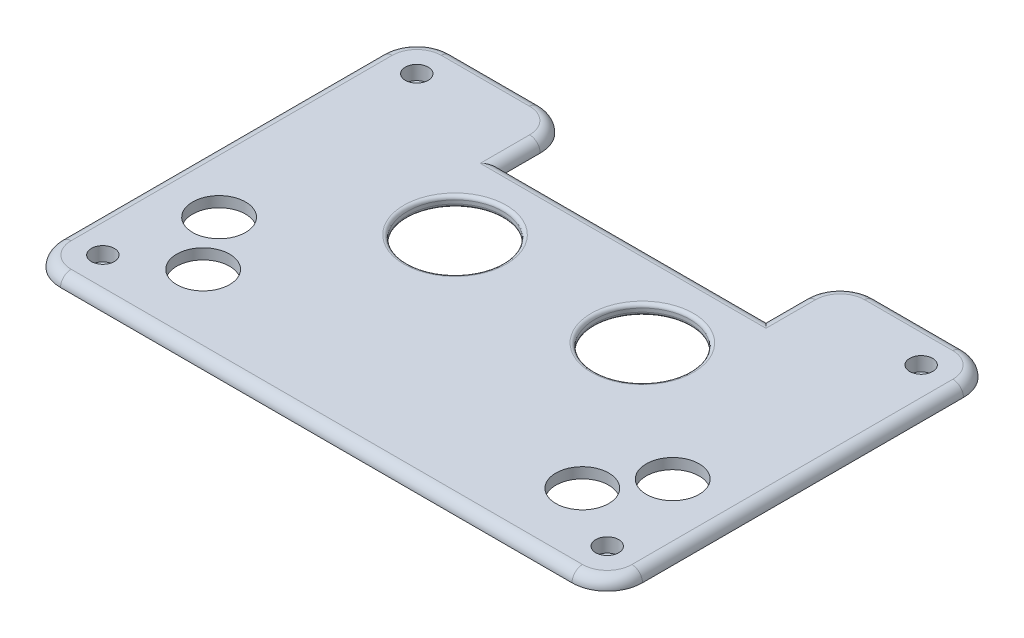
SolidWorks part; units mm, degrees
ref_plane "Front Plane" through (0, 0, 0) normal (0, 0, 1) x (1, 0, 0)
ref_plane "Top Plane" through (0, 0, 0) normal (0, 1, 0) x (1, 0, 0)
ref_plane "Right Plane" through (0, 0, 0) normal (1, 0, 0) x (0, 0, -1)
sketch "Sketch1" plane through (0, 0, 0) normal (0, 1, 0) x (1, 0, 0)
  line L0 (37.5, 55.5) -> (37.5, 34.5)
  line L1 (-82.5, 55.5) -> (82.5, 55.5) construction
  line L2 (-82.5, 55.5) -> (-82.5, -55.5) construction
  line L3 (-82.5, -55.5) -> (82.5, -55.5) construction
  line L4 (82.5, 55.5) -> (82.5, -55.5) construction
  line L5 (-82.5, 55.5) -> (82.5, -55.5) construction
  line L6 (-82.5, -55.5) -> (82.5, 55.5) construction
  line L7 (-82.5, 55.5) -> (-37.5, 55.5) construction
  line L8 (-82.5, 55.5) -> (-82.5, 24.5) construction
  line L10 (-37.5, 55.5) -> (-37.5, 34.5) construction
  line L11 (82.5, 55.5) -> (37.5, 55.5) construction
  line L12 (82.5, 55.5) -> (82.5, 24.5) construction
  line L14 (37.5, 55.5) -> (37.5, 34.5) construction
  line L15 (37.5, 34.5) -> (-37.5, 34.5)
  line L16 (-37.5, 34.5) -> (-37.5, 55.5)
  line L17 (-37.5, 55.5) -> (-82.5, 55.5)
  line L18 (-82.5, 55.5) -> (-82.5, -55.5)
  line L19 (-82.5, -55.5) -> (82.5, -55.5)
  line L20 (82.5, -55.5) -> (82.5, 55.5)
  line L21 (82.5, 55.5) -> (37.5, 55.5)
  point P0 (0, 0)
  dimension "D1" = 45
  dimension "D2" = 21
  dimension "D3" = 75
  dimension "D4" = 165
  dimension "D5" = 45
  dimension "D6" = 111
extrude "Boss-Extrude1" add sketch "Sketch1" along normal blind 3 contours L2 L1 L4 L3 | L21 L0 L15 L16 L17 L18 L19 L20
fillet "Fillet1" radius 10 2 edges at (-82.5, 1.5, 55.5) (82.5, 1.5, 55.5)
fillet "Fillet4" radius 10 4 edges at (-82.5, 1.5, -55.5) (-37.5, 1.5, -55.5) (37.5, 1.5, -55.5) (82.5, 1.5, -55.5)
sketch "Sketch3" plane through (0, 3, 0) normal (0, 1, 0) x (1, 0, 0)
  line L0 (26.55, -6.5946) -> (26.55, 27.4054) construction
  line L7 (39.55, -6.5946) -> (13.55, -6.5946) construction
  line L8 (39.55, -6.5946) -> (39.55, 27.4054) construction
  line L9 (39.55, 27.4054) -> (13.55, 27.4054) construction
  line L10 (13.55, -6.5946) -> (13.55, 27.4054) construction
  line L12 (0, -52.5) -> (0, 31.5) construction
  circle A0 centre (36.6, 24.4554) radius 2.35 construction
  circle A1 centre (36.6, 24.4554) radius 5 construction
  circle A4 centre (36.6, -1.8446) radius 2.35 construction
  circle A5 centre (36.6, -1.8446) radius 5 construction
  circle A6 centre (16.4002, -1.756) radius 5 construction
  circle A7 centre (16.4002, -1.756) radius 2.35 construction
  circle A16 centre (16.5, 24.4554) radius 5 construction
  circle A17 centre (16.5, 24.4554) radius 2.35 construction
  circle A34 centre (26.55, 10.4054) radius 13.5
  circle A35 centre (-26.55, 10.4054) radius 13.5
  dimension "D11" = 4.7
  dimension "D12" = 10
  dimension "D15" = 4.7
  dimension "D16" = 10
  dimension "D2" = 34
  dimension "D3" = 26
  dimension "D9" = 20.2
  dimension "D10" = 27
  dimension "D4" = 4.75
  dimension "D5" = 2.95
  dimension "D6" = 2.95
  dimension "D7" = 2.95
sketch "Sketch5" plane through (0, 3, 0) normal (0, 1, 0) x (1, 0, 0)
  line L0 (-47.5547, -42.6607) -> (-70.4978, -9.8946) construction
  line L1 (-55.7463, -48.3965) -> (-78.6893, -15.6304) construction
  line L2 (-55.7463, -48.3965) -> (-39.3632, -36.925) construction
  line L3 (-39.3632, -36.925) -> (-62.3063, -4.1589) construction
  line L4 (-78.6893, -15.6304) -> (-62.3063, -4.1589) construction
  line L5 (0, -52.5) -> (0, 31.5) construction
  line L8 (-67.2178, -32.0134) -> (-50.8347, -20.5419) construction
  circle A0 centre (-49.2755, -40.2033) radius 1.6 construction
  circle A1 centre (-68.7771, -12.3521) radius 1.6 construction
  circle A2 centre (-49.2755, -40.2033) radius 4 construction
  circle A3 centre (-68.7771, -12.3521) radius 4 construction
  circle A9 centre (-53.7494, -33.8139) radius 7.5
  circle A10 centre (-64.3032, -18.7415) radius 7.5
  circle A11 centre (64.3032, -18.7415) radius 7.5
  circle A12 centre (53.7494, -33.8139) radius 7.5
  dimension "D3" = 3
  dimension "D4" = 3.2
  dimension "D5" = 3.2
  dimension "D6" = 3
  dimension "D7" = 8
  dimension "D8" = 8
  dimension "D9" = 9.2
  dimension "D10" = 15
  dimension "D1" = 40
  dimension "D2" = 20
sketch "Sketch6" plane through (0, 3, 0) normal (0, 1, 0) x (1, 0, 0)
  line L0 (0, -52.5) -> (0, 31.5) construction
  line L14 (76.5, 39.5) -> (66.5, 39.5)
  line L15 (66.5, 49.5) -> (66.5, 39.5)
  line L16 (72.5, 49.5) -> (66.5, 49.5)
  line L18 (76.5, 45.5) -> (76.5, 39.5)
  line L19 (66.5, 44.5) -> (76.5, 44.5) construction
  line L34 (79.5, 0) -> (-79.5, 0) construction
  line L36 (76.5, -45.5) -> (76.5, -39.5)
  line L37 (72.5, -49.5) -> (66.5, -49.5)
  line L38 (66.5, -49.5) -> (66.5, -39.5)
  line L39 (76.5, -39.5) -> (66.5, -39.5)
  line L40 (-76.5, 39.5) -> (-66.5, 39.5)
  line L41 (-76.5, 45.5) -> (-76.5, 39.5)
  line L42 (-66.5, 49.5) -> (-66.5, 39.5)
  line L43 (-72.5, 49.5) -> (-66.5, 49.5)
  line L44 (-72.5, -49.5) -> (-66.5, -49.5)
  line L45 (-76.5, -45.5) -> (-76.5, -39.5)
  line L46 (-76.5, -39.5) -> (-66.5, -39.5)
  line L47 (-66.5, -49.5) -> (-66.5, -39.5)
  arc A11 (76.5, 45.5) -> (72.5, 49.5) centre (72.5, 45.5) ccw
  arc A22 (76.5, -45.5) -> (72.5, -49.5) centre (72.5, -45.5) cw
  arc A23 (-76.5, 45.5) -> (-72.5, 49.5) centre (-72.5, 45.5) cw
  arc A24 (-76.5, -45.5) -> (-72.5, -49.5) centre (-72.5, -45.5) ccw
  point P33 (71.5, 44.5)
  dimension "D3" = 10
  dimension "D4" = 10
extrude "Boss-Extrude4" add sketch "Sketch6" against normal blind 6.9
fillet "Fillet5" radius 3 14 edges at (-37.5, 3, -40) (-40.4289, 3, -52.5711) (-60, 3, -55.5) (-79.5711, 3, -52.5711) (-82.5, 3, 0) (-79.5711, 3, 52.5711) (0, 3, 55.5) (79.5711, 3, 52.5711) (82.5, 3, 0) (79.5711, 3, -52.5711) (37.5, 3, -40) (40.4289, 3, -52.5711) (0, 3, -34.5) (60, 3, -55.5)
sketch "Sketch7" plane through (0, -3.9, 0) normal (0, -1, 0) x (1, 0, 0)
  line L0 (71.5, -39.5) -> (71.5, -49.5) construction
  line L1 (66.5, -39.5) -> (76.5, -39.5) construction
  line L2 (72.5, -49.5) -> (66.5, -49.5) construction
  line L3 (0, 0) -> (0, -47.6531) construction
  line L4 (0, 0) -> (0, 59.7822) construction
  line L5 (0, 0) -> (-99.6229, 0) construction
  line L6 (0, 0) -> (103.0572, 0) construction
  circle A0 centre (71.5, -44.5) radius 2
  circle A1 centre (-71.5, -44.5) radius 2
  circle A2 centre (-71.5, 44.5) radius 2
  circle A3 centre (71.5, 44.5) radius 2
  dimension "D1" = 4
extrude "Cut-Extrude2" cut sketch "Sketch7" against normal through all
sketch "Sketch8" plane through (0, 3, 0) normal (0, 1, 0) x (1, 0, 0)
  line L0 (73.5, 44.5) -> (69.5, 44.5) construction
  line L1 (79.5, 0) -> (-79.5, 0) construction
  line L4 (0, -52.5) -> (0, 31.5) construction
  circle A1 centre (71.5, 44.5) radius 3.25
  circle A2 centre (71.5, -44.5) radius 3.25
  circle A3 centre (-71.5, -44.5) radius 3.25
  circle A4 centre (-71.5, 44.5) radius 3.25
  dimension "D1" = 6.5
extrude "Cut-Extrude3" cut sketch "Sketch8" against normal blind 4
extrude "Cut-Extrude4" cut sketch "Sketch3" against normal through all
fillet "Fillet6" radius 1 4 edges at (-26.55, 0, 3.0946) (26.55, 0, 3.0946) (-26.55, 3, -23.9054) (26.55, 3, 3.0946)
extrude "Cut-Extrude5" cut sketch "Sketch5" against normal through all
fillet "Fillet7" radius 1.9 20 edges at (-75.3284, 0, -48.3284) (-76.5, 0, -42.5) (-71.5, 0, -39.5) (-66.5, 0, -44.5) (-69.5, 0, -49.5) (76.5, 0, -42.5) (75.3284, 0, -48.3284) (69.5, 0, -49.5) (66.5, 0, -44.5) (71.5, 0, -39.5) (76.5, 0, 42.5) (71.5, 0, 39.5) (66.5, 0, 44.5) (69.5, 0, 49.5) (75.3284, 0, 48.3284) (-66.5, 0, 44.5) (-71.5, 0, 39.5) (-76.5, 0, 42.5) (-75.3284, 0, 48.3284) (-69.5, 0, 49.5)
